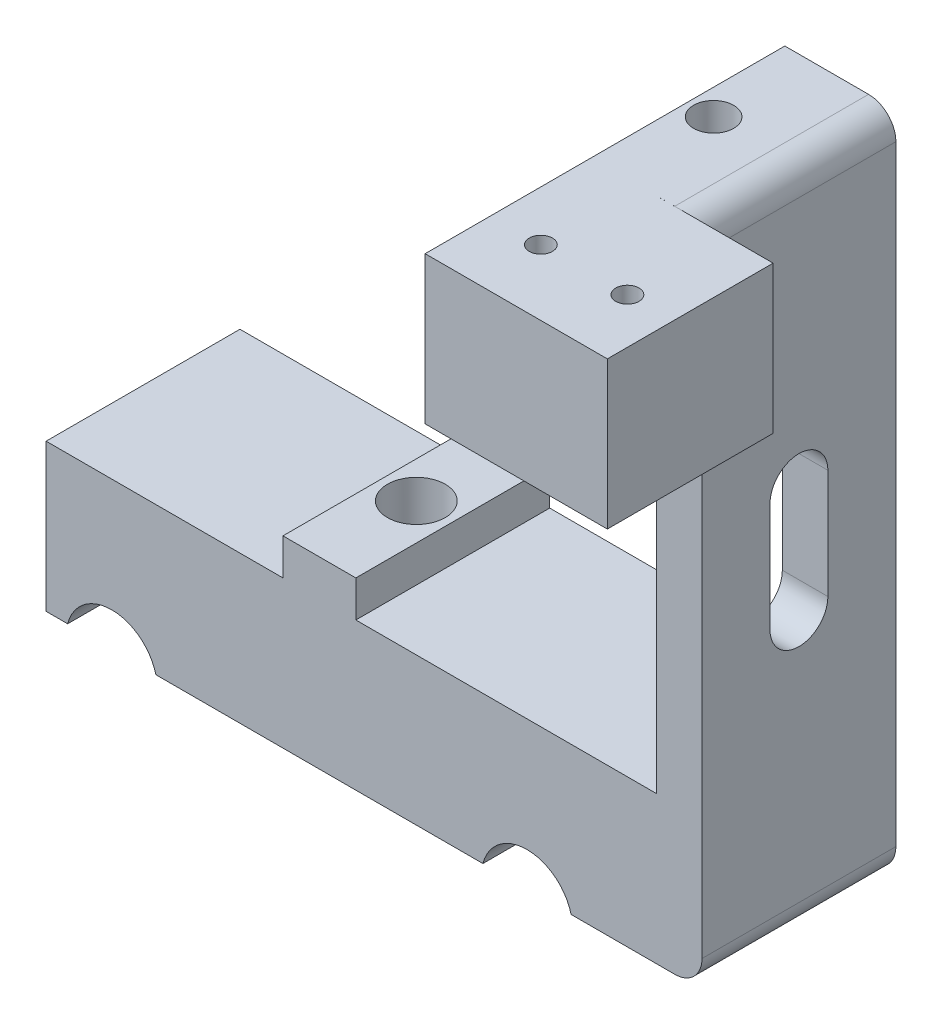
SolidWorks part; units mm, degrees
ref_plane "Front Plane" through (0, 0, 0) normal (0, 0, 1) x (1, 0, 0)
ref_plane "Top Plane" through (0, 0, 0) normal (0, 1, 0) x (1, 0, 0)
ref_plane "Right Plane" through (0, 0, 0) normal (1, 0, 0) x (0, 0, -1)
sketch "Sketch2" plane through (0, 0, 0) normal (0, 0, 1) x (1, 0, 0)
  line L0 (10.1, 0) -> (-10.1, 0)
  line L1 (-10.1, 0) -> (-10.1, 1.7099)
  line L2 (-10.1, 1.7099) -> (-6.2548, 7)
  line L3 (-6.2548, 7) -> (6.2548, 7)
  line L4 (0, 7) -> (0, 0)
  line L5 (0, 0) -> (0, 9.2516) construction
  line L6 (10.1, 1.7099) -> (6.2548, 7)
  line L7 (10.1, 0) -> (10.1, 1.7099)
  dimension "D1" = 20.2
  dimension "D2" = 7
extrude "Boss-Extrude1" add sketch "Sketch2" along normal blind 10.8 contours L4 L3 L2 L1 L0 | L0 L7 L6 L3 L4 region at (4.4168, 3.2082, 0) region at (-4.4168, 3.2082, 0)
sketch "Sketch4" plane through (0, 0, 0) normal (0, 0, 1) x (1, 0, 0)
  line L0 (-4, 0) -> (-4, -4.8)
  line L1 (10.1, 0) -> (-10.1, 0) construction
  line L2 (-4, -4.8) -> (-30, -4.8)
  line L3 (-30, -4.8) -> (-30, -29.8)
  line L4 (-30, -29.8) -> (30, -29.8)
  line L5 (0, 0) -> (0, -29.8) construction
  line L6 (0, -29.8) -> (0, 0)
  line L7 (4, 0) -> (-4, 0)
  line L8 (0, 0) -> (0, -30.5381) construction
  line L9 (30, -4.8) -> (30, -29.8)
  line L10 (4, -4.8) -> (30, -4.8)
  line L11 (4, 0) -> (4, -4.8)
  line L13 (-30, -20.98) -> (30, -20.98)
  line L14 (-30, -20.98) -> (-30, -23.48)
  line L15 (-30, -23.48) -> (30, -23.48)
  line L16 (30, -20.98) -> (30, -23.48)
  dimension "D1" = 4.8
  dimension "D2" = 4
  dimension "D3" = 25
  dimension "D4" = 60
  dimension "D6" = 8.82
extrude "Boss-Extrude2" add sketch "Sketch4" along normal mid plane 21.28 contours L6 L7 L0 L2 L3 L4 | L11 L7 L6 L4 L9 L10 region at (-14.5054, -12.4909, 0) region at (14.5054, -12.4909, 0)
sketch "Sketch5" plane through (0, 0, 0) normal (0, 0, 1) x (1, 0, 0)
  line L0 (-29.791, -22.2274) -> (26.9734, -22.2274) construction
  line L3 (0, -20.98) -> (0, 7) construction
  line L5 (-6.2548, 7) -> (6.2548, 7) construction
  line L20 (-30, -20.98) -> (30, -20.98) construction
  circle A0 centre (-22.791, -22.2274) radius 5
  circle A1 centre (22.791, -22.2274) radius 5
  dimension "D1" = 7
extrude "Cut-Extrude1" cut sketch "Sketch5" along normal through all both and the other way through all
fillet "Fillet1" radius 1 6 edges at (-10.1, 0, 5.4) (-10.1, 1.7099, 5.4) (-6.2548, 7, 5.4) (6.2548, 7, 5.4) (10.1, 0, 5.4) (10.1, 1.7099, 5.4)
sketch "Sketch6" plane through (30, 0, 0) normal (1, 0, 0) x (0, 0, -1)
  line L0 (-10.64, -20.98) -> (10.64, -20.98) construction
  line L1 (-10.64, -4.8) -> (10.64, -4.8)
  line L2 (-10.64, -4.8) -> (-10.64, -20.98)
  line L3 (-10.64, -20.98) -> (10.64, -20.98)
  line L4 (10.64, -4.8) -> (10.64, -20.98)
extrude "Boss-Extrude3" add sketch "Sketch6" along normal blind 12
sketch "Sketch7" plane through (0, -4.8, 0) normal (0, 1, 0) x (1, 0, 0)
  line L0 (4, -10.64) -> (42, -10.64) construction
  line L1 (42, 10.6413) -> (37, 10.6413)
  line L2 (42, 10.6413) -> (42, -10.64)
  line L3 (42, -10.64) -> (37, -10.64)
  line L4 (37, 10.6413) -> (37, -10.64)
  dimension "D1" = 5
extrude "Boss-Extrude4" add sketch "Sketch7" along normal blind 56.83
sketch "Sketch8" plane through (37, 0, 0) normal (-1, 0, 0) x (0, 0, 1)
  line L0 (-10.6413, 52.03) -> (-10.6413, -4.8) construction
  line L1 (10.643, 52.03) -> (-10.6413, 52.03)
  line L2 (10.643, 52.03) -> (10.643, 35.85)
  line L3 (10.643, 35.85) -> (-10.6413, 35.85)
  line L4 (-10.6413, 52.03) -> (-10.6413, 35.85)
  dimension "D1" = 16.18
extrude "Boss-Extrude5" add sketch "Sketch8" along normal blind 7.19
fillet "Fillet3" radius 3 2 edges at (42, 52.03, -0.0007) (42, -20.98, 0)
sketch "Sketch9" plane through (0, -20.98, 0) normal (0, -1, 0) x (1, 0, 0)
  line L0 (27.6329, 0) -> (27.6329, 10.8) construction
  line L2 (27.6329, 10.64) -> (39, 10.64) construction
  circle A0 centre (32.6329, 0) radius 2.2
  dimension "D1" = 5
  dimension "D2" = 10.64
extrude "Cut-Extrude2" cut sketch "Sketch9" against normal through all
sketch "Sketch10" plane through (0, -20.98, 0) normal (0, -1, 0) x (1, 0, 0)
  line L2 (-17.9491, 0) -> (-17.9491, 10.8) construction
  line L3 (-17.9491, 10.64) -> (17.9491, 10.64) construction
  circle A0 centre (0.0009, 0) radius 3.175
  dimension "D1" = 10.64
  dimension "D3" = 6.35
  dimension "D2" = 17.95
extrude "Cut-Extrude3" cut sketch "Sketch10" against normal through all
sketch "Sketch11" plane through (0, 0, 10.8) normal (0, 0, 1) x (1, 0, 0)
  line L0 (9.1, 0) -> (-9.1, 0) construction
  line L1 (-12.6098, 8.9215) -> (12.3675, 8.9215)
  line L2 (-12.6098, 8.9215) -> (-12.6098, -0.8)
  line L3 (-12.6098, -0.8) -> (12.3675, -0.8)
  line L4 (12.3675, 8.9215) -> (12.3675, -0.8)
  dimension "D1" = 0.8
extrude "Cut-Extrude4" cut sketch "Sketch11" against normal through all
sketch "Sketch12" plane through (42, 0, 0) normal (1, 0, 0) x (0, 0, -1)
  line L0 (-3.175, 21.525) -> (-3.175, 9.525)
  line L1 (10.6413, 49.03) -> (-10.64, 49.03) construction
  line L2 (3.175, 9.525) -> (3.175, 21.525)
  arc A0 (3.175, 21.525) -> (-3.175, 21.525) centre (0, 21.525) ccw
  arc A1 (-3.175, 9.525) -> (3.175, 9.525) centre (0, 9.525) ccw
  dimension "D1" = 27.505
  dimension "D2" = 12
extrude "Cut-Extrude5" cut sketch "Sketch12" against normal through all
sketch "Sketch13" plane through (0, 0, 10.643) normal (0, 0, 1) x (1, 0, 0)
  line L1 (29.81, 52.03) -> (49.81, 52.03)
  line L2 (29.81, 52.03) -> (29.81, 35.85)
  line L3 (29.81, 35.85) -> (49.81, 35.85)
  line L4 (49.81, 52.03) -> (49.81, 35.85)
  point P5 (29.81, 35.85)
  dimension "D1" = 20
extrude "Boss-Extrude6" add sketch "Sketch13" along normal blind 18.2
sketch "Sketch14" plane through (0, 52.03, 0) normal (0, 1, 0) x (1, 0, 0)
  line L0 (49.81, -28.843) -> (49.81, -10.643) construction
  line L1 (49.81, -28.843) -> (29.81, -28.843) construction
  line L2 (29.81, -18.643) -> (49.81, -18.643) construction
  line L3 (29.81, -28.843) -> (29.81, 10.6413) construction
  circle A0 centre (35.31, -21.643) radius 1.275
  circle A1 centre (44.81, -21.643) radius 1.275
  dimension "D1" = 14.5
  dimension "D2" = 9.5
  dimension "D3" = 3
  dimension "D4" = 10.2
extrude "Cut-Extrude6" cut sketch "Sketch14" against normal through all
